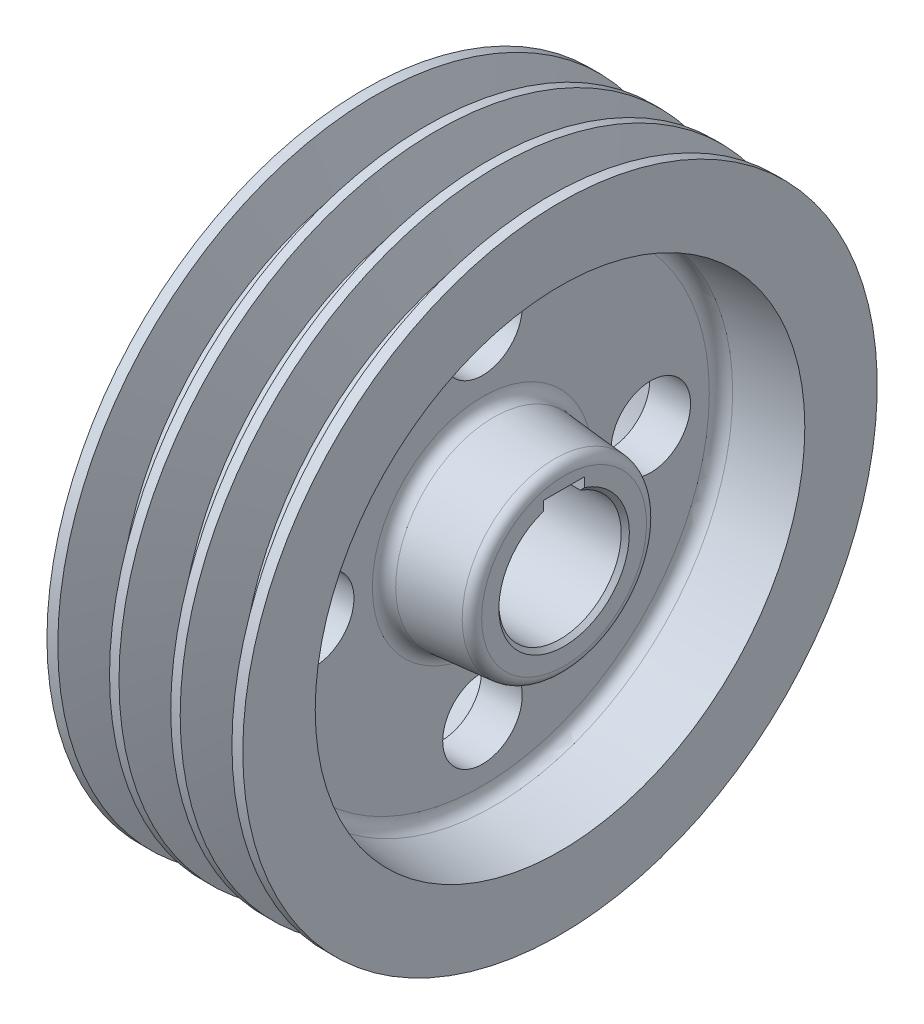
SolidWorks part; units mm, degrees
ref_plane "前视基准面" through (0, 0, 0) normal (0, 0, 1) x (1, 0, 0)
ref_plane "上视基准面" through (0, 0, 0) normal (0, 1, 0) x (1, 0, 0)
ref_plane "右视基准面" through (0, 0, 0) normal (1, 0, 0) x (0, 0, -1)
sketch "草图1" plane through (0, 0, 0) normal (0, 0, 1) x (1, 0, 0)
  line L0 (0, 0) -> (64.8368, 0) construction
  line L1 (-1, 15) -> (-1, 22.5)
  line L2 (0, 77.75) -> (48, 77.75)
  line L3 (48, 77.75) -> (48, 60)
  line L4 (-1, 22.5) -> (-30, 22.5) construction
  line L5 (19, 24.2498) -> (19, 58.3377)
  line L6 (49, 15) -> (-1, 15)
  line L7 (2.6592, 77.75) -> (6.1599, 66.3) construction
  line L8 (6.1599, 66.3) -> (11.8401, 66.3) construction
  line L9 (11.8401, 66.3) -> (15.3408, 77.75) construction
  line L10 (0, 75) -> (48, 75) construction
  line L11 (9, 66.3) -> (9, 15) construction
  line L12 (44, 60) -> (0, 60) construction
  line L13 (48, 60) -> (79, 60) construction
  line L14 (29, 58.3377) -> (29, 24.2498)
  line L15 (5, 22.5) -> (49, 22.5) construction
  line L16 (24, 15) -> (24, 77.75) construction
  line L17 (49, 22.5) -> (49, 15)
  line L18 (0, 60) -> (0, 77.75)
  line L19 (19, 51) -> (29, 51) construction
  line L20 (19, 31.5) -> (29, 31.5) construction
  line L21 (48, 60) -> (48, 51) construction
  line L22 (48, 51) -> (29, 51) construction
  line L23 (29, 31.5) -> (49, 31.5) construction
  line L24 (49, 31.5) -> (49, 22.5) construction
  line L25 (29, 58.3377) -> (48, 60)
  line L26 (19, 58.3377) -> (0, 60)
  line L27 (19, 24.2498) -> (-1, 22.5)
  line L28 (29, 24.2498) -> (49, 22.5)
  point P17 (3.5, 75)
  point P18 (14.5, 75)
  dimension "d2" = 120
  dimension "L" = 50
  dimension "B" = 48
  dimension "d" = 30
  dimension "d1" = 45
  dimension "D3" = 5
  dimension "D4" = 5
  dimension "dd" = 150
  dimension "f" = 9
  dimension "槽轮角" = 34
  dimension "bd" = 11
  dimension "hf" = 8.7
  dimension "ha" = 2.75
  dimension "da" = 155.5
  dimension "S" = 10
  dimension "S2" = 9
revolve "旋转1" add sketch "草图1" angle 360 about L0
sketch "草图2" plane through (0, 0, 0) normal (0, 0, 1) x (1, 0, 0)
  line L0 (11.8401, 66.3) -> (15.3408, 77.75) construction
  line L1 (6.1599, 66.3) -> (11.8401, 66.3) construction
  line L2 (2.6592, 77.75) -> (6.1599, 66.3) construction
  line L3 (11.8401, 66.3) -> (15.3408, 77.75)
  line L4 (6.1599, 66.3) -> (11.8401, 66.3)
  line L5 (2.6592, 77.75) -> (6.1599, 66.3)
  line L6 (2.6592, 77.75) -> (15.3408, 77.75)
  line L7 (0, 0) -> (123, 0) construction
revolve "切除-旋转1" cut sketch "草图2" angle 360 about L7
pattern_linear "轮槽数" count 3 spacing 15 along (1, 0, 0) of "切除-旋转1"
chamfer "倒角1" distance 1 angle 45 2 edges at (-1, 0, 15) (49, 0, 15)
sketch "草图4" plane through (-1, 0, 0) normal (-1, 0, 0) x (0, 0, 1)
  line L1 (-5, 14.1421) -> (5, 14.1421)
  line L2 (-5, 14.1421) -> (-5, 17.5)
  line L3 (-5, 17.5) -> (5, 17.5)
  line L4 (5, 14.1421) -> (5, 17.5)
  circle A0 centre (0, 0) radius 15 construction
  point P6 (2.5, 17.5)
  dimension "键槽高度" = 17.5
  dimension "键槽宽度" = 10
  dimension "t1" = 2.5
extrude "切除-拉伸1" cut sketch "草图4" against normal through all
fillet "圆角1" radius 3 4 edges at (29, 0, 58.3377) (19, 0, 24.2498) (19, 0, 58.3377) (29, 0, 24.2498)
fillet "圆角2" radius 2.5 2 edges at (49, 0, 22.5) (-1, 0, 22.5)
sketch "草图5" plane through (0, 0, 0) normal (1, 0, 0) x (0, 0, -1)
  line L0 (0, 66.3) -> (0, 15) construction
  circle A0 centre (0, 41.25) radius 9.75
extrude "切除-拉伸2" cut sketch "草图5" along normal through all
pattern_circular "圆孔个数" count 4 over 360 of "切除-拉伸2"
equation "\"B@草图1\" =  ( \"z@轮槽数\" - 1 )  * \"e@轮槽数\" +2 *  \"f@草图1\""
equation "\"键槽高度@草图4\" = \"d@草图1\" / 2 + \"t1@草图4\""
